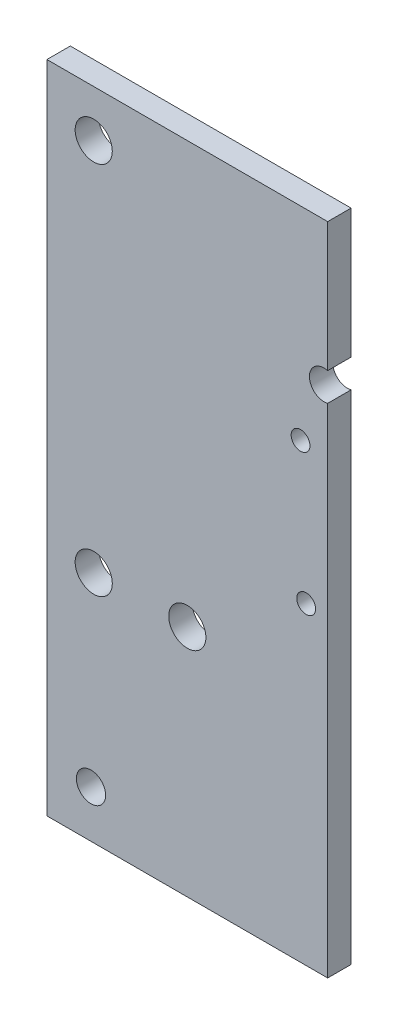
SolidWorks part; units mm, degrees
ref_plane "Front Plane" through (0, 0, 0) normal (1, 0, 0) x (0, 1, 0)
ref_plane "Top Plane" through (0, 0, 0) normal (0, 0, 1) x (0, 1, 0)
ref_plane "Right Plane" through (0, 0, 0) normal (0, 1, 0) x (-1, 0, 0)
sketch "Sketch2" plane through (0, 0, 0) normal (0, 0, 1) x (0, 1, 0)
  line L1 (0, 0) -> (177.8, 0)
  line L2 (0, 0) -> (0, 76.2)
  line L3 (0, 76.2) -> (177.8, 76.2)
  line L4 (177.8, 0) -> (177.8, 76.2)
  line L5 (63.5, 63.5) -> (165.1, 63.5) construction
  line L6 (63.5, 63.5) -> (63.5, 38.1) construction
  line L7 (63.5, 38.1) -> (165.1, 38.1) construction
  line L8 (165.1, 63.5) -> (165.1, 38.1) construction
  line L9 (63.5, 38.1) -> (124.236, 38.1) construction
  line L10 (63.5, 38.1) -> (63.5, 49.6176) construction
  line L11 (63.5, 49.6176) -> (124.236, 49.6176) construction
  line L12 (124.236, 38.1) -> (124.236, 49.6176) construction
  line L13 (63.5, 38.1) -> (139.7, 38.1) construction
  line L14 (63.5, 38.1) -> (63.5, 45.5554) construction
  line L15 (63.5, 45.5554) -> (139.7, 45.5554) construction
  line L16 (139.7, 38.1) -> (139.7, 45.5554) construction
  dimension "D2" = 12.7
  dimension "D3" = 12.7
  dimension "D4" = 25.4
  dimension "D5" = 177.8
  dimension "D6" = 76.2
  dimension "D7" = 11.5176
  dimension "D8" = 60.736
  dimension "D9" = 7.4554
  dimension "D10" = 76.2
  dimension "D11" = 101.6
extrude "Boss-Extrude1" add sketch "Sketch2" along normal blind 6.35
hole_wizard "3/8 Clearance Hole1" positions "Sketch3" profile "Sketch4" hole size "3/8" standard "ANSI Inch" end condition through all
sketch "Sketch3" plane through (0, 0, 6.35) normal (0, 0, 1) x (1, 0, 0)
  point P0 (-38.1, 63.5)
  point P3 (-63.5, 63.5)
  point P6 (-63.5, 165.1)
sketch "Sketch4" plane through (-38.1, 63.5, 6.35) normal (1, 0, 0) x (0, -1, 0)
  line L0 (0, 0) -> (0, 6.35)
  line L1 (0, 6.35) -> (5.0419, 6.35)
  line L2 (5.0419, 6.35) -> (5.0419, 0)
  line L5 (5.0419, 0) -> (0, 0)
  line L11 (0, -6.35) -> (0, 107.95) construction
  dimension "Thru Hole Dia." = 10.0838
  dimension "Thru Hole Depth" = 6.35
hole_wizard "Tap Drill for 1/4-20 Tap1" positions "Sketch7" profile "Sketch6" hole size "1/4-20" standard "ANSI Inch" end condition through all
sketch "Sketch7" plane through (0, 0, 6.35) normal (0, 0, 1) x (1, 0, 0)
  circle A4 centre (-5.8278, 85.09) radius 152.3975 construction
  circle A5 centre (-7.366, 122.682) radius 150.368 construction
  point P0 (-5.8278, 85.09)
  point P3 (-7.366, 122.682)
sketch "Sketch6" plane through (-5.8278, 85.09, 6.35) normal (1, 0, 0) x (0, -1, 0)
  line L0 (0, 0) -> (0, 6.35)
  line L1 (0, 6.35) -> (2.5527, 6.35)
  line L2 (2.5527, 6.35) -> (2.5527, 0)
  line L5 (2.5527, 0) -> (0, 0)
  line L11 (0, -6.35) -> (0, 107.95) construction
  dimension "Thru Hole Dia." = 5.1054
  dimension "Thru Hole Depth" = 6.35
sketch "Sketch8" plane through (0, 0, 6.35) normal (0, 0, 1) x (1, 0, 0)
  line L0 (-5.8278, 85.09) -> (-76.2, 21.1011) construction
  line L1 (-7.366, 122.682) -> (-50.9894, 177.8) construction
  line L2 (0, 0) -> (0, 177.8) construction
  line L3 (-76.2, 177.8) -> (-76.2, 0) construction
  line L6 (0, 177.8) -> (-76.2, 177.8) construction
  line L7 (-77.5678, 19.8574) -> (-64.2396, 12.8003) construction
  line L8 (-12.8106, 129.5613) -> (-0.985, 138.9207) construction
  dimension "D1" = 38.36
  dimension "D2" = 47.72
  dimension "D3" = 15.0812
  dimension "D4" = 15.0812
hole_wizard "Tap Drill for 3/8-16 Tap2" positions "Sketch9" profile "Sketch10" hole size "3/8-16" standard "ANSI Inch"
sketch "Sketch9" plane through (0, 0, 6.35) normal (0, 0, 1) x (1, 0, 0)
  point P0 (-64.2396, 12.8003)
  point P3 (-0.985, 138.9207)
sketch "Sketch10" plane through (-64.2396, 12.8003, 6.35) normal (1, 0, 0) x (0, -1, 0)
  line L0 (0, 0) -> (0, 15.0847)
  line L1 (0, 15.0847) -> (3.9687, 12.7)
  line L2 (3.9687, 12.7) -> (3.9687, 0)
  line L5 (3.9687, 0) -> (0, 0)
  line L10 (0, 15.0847) -> (-3.9688, 12.7) construction
  line L11 (0, -6.35) -> (0, 107.95) construction
  dimension "Hole Dia." = 7.9375
  dimension "Hole Depth" = 12.7
  dimension "Drill Angle" = 118
